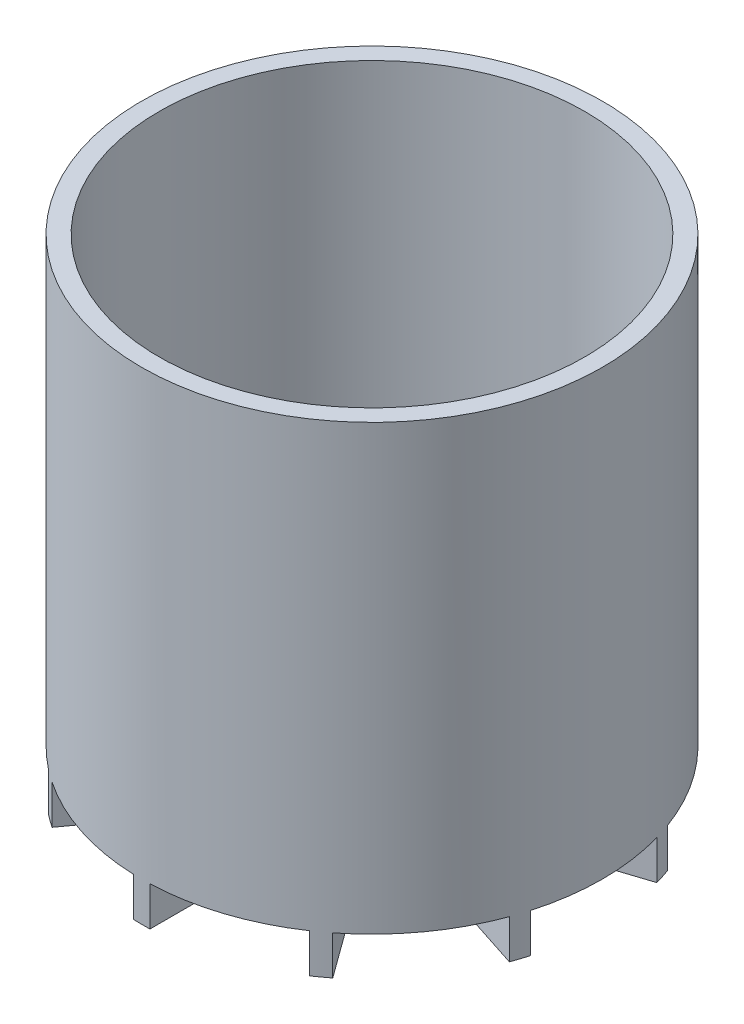
SolidWorks part; units mm, degrees
ref_plane "Front Plane" through (0, 0, 0) normal (0, 0, 1) x (1, 0, 0)
ref_plane "Top Plane" through (0, 0, 0) normal (0, 1, 0) x (1, 0, 0)
ref_plane "Right Plane" through (0, 0, 0) normal (1, 0, 0) x (0, 0, -1)
sketch "Sketch1" plane through (0, 0, 0) normal (0, 1, 0) x (1, 0, 0)
  circle A0 centre (0, 0) radius 38.1
  dimension "D1" = 76.2
extrude "Boss-Extrude1" add sketch "Sketch1" along normal blind 76.2
shell "Shell2" thickness 3.175 removed face at (0, 76.2, 38.1) outward yes
ref_axis "Axis1" through (0, 76.2, 0) along (0, -1, 0)
sketch "Sketch2" plane through (0, -3.175, 0) normal (0, -1, 0) x (-1, 0, 0)
  line L0 (0, 0) -> (0, 41.275)
  line L1 (-1.5, -41.275) -> (-1.5, 41.275)
  line L2 (-1.5, -41.275) -> (1.5, -41.275)
  line L3 (-1.5, 41.275) -> (1.5, 41.275)
  line L4 (1.5, -41.275) -> (1.5, 41.275)
  line L5 (-1.5, -41.275) -> (1.5, 41.275) construction
  line L6 (-1.5, 41.275) -> (1.5, -41.275) construction
  line L7 (-23.0473, -34.2739) -> (25.4744, 32.5105)
  line L8 (-25.4744, -32.5105) -> (23.0473, 34.2739)
  line L9 (-25.4744, -32.5105) -> (-23.0473, -34.2739)
  line L10 (23.0473, 34.2739) -> (25.4744, 32.5105)
  line L11 (-38.7913, -14.1813) -> (39.7184, 11.3281)
  line L12 (-39.7184, -11.3281) -> (38.7913, 14.1813)
  line L13 (-39.7184, -11.3281) -> (-38.7913, -14.1813)
  line L14 (38.7913, 14.1813) -> (39.7184, 11.3281)
  line L15 (-39.7184, 11.3281) -> (38.7913, -14.1813)
  line L16 (-38.7913, 14.1813) -> (39.7184, -11.3281)
  line L17 (-38.7913, 14.1813) -> (-39.7184, 11.3281)
  line L18 (39.7184, -11.3281) -> (38.7913, -14.1813)
  line L19 (-25.4744, 32.5105) -> (23.0473, -34.2739)
  line L20 (-23.0473, 34.2739) -> (25.4744, -32.5105)
  line L21 (-23.0473, 34.2739) -> (-25.4744, 32.5105)
  line L22 (25.4744, -32.5105) -> (23.0473, -34.2739)
  line L23 (-1.5, 41.275) -> (-1.5, -41.275)
  line L24 (1.5, 41.275) -> (1.5, -41.275)
  line L25 (1.5, 41.275) -> (-1.5, 41.275)
  line L26 (1.5, -41.275) -> (-1.5, -41.275)
  circle A1 centre (0, 0) radius 41.275 construction
  circle A2 centre (0, 0) radius 41.275
  dimension "D1" = 3
  dimension "D2" = 6
extrude "Boss-Extrude2" add sketch "Sketch2" along normal blind 7 contours L4 L3 L1 L2 | L7 L10 L8 L9 | L11 L14 L12 L13 | L15 L18 L16 L17 | L20 L22 L19 L21
sketch "Sketch3" plane through (0, -3.175, 0) normal (0, -1, 0) x (1, 0, 0)
  circle A0 centre (0, 0) radius 41.275
  circle A1 centre (0, 0) radius 61.9063
extrude "Cut-Extrude1" cut sketch "Sketch3" against normal through all both and the other way through all
scale "Scale1" scale about centroid uniform scaling yes scale factor 0.615385
